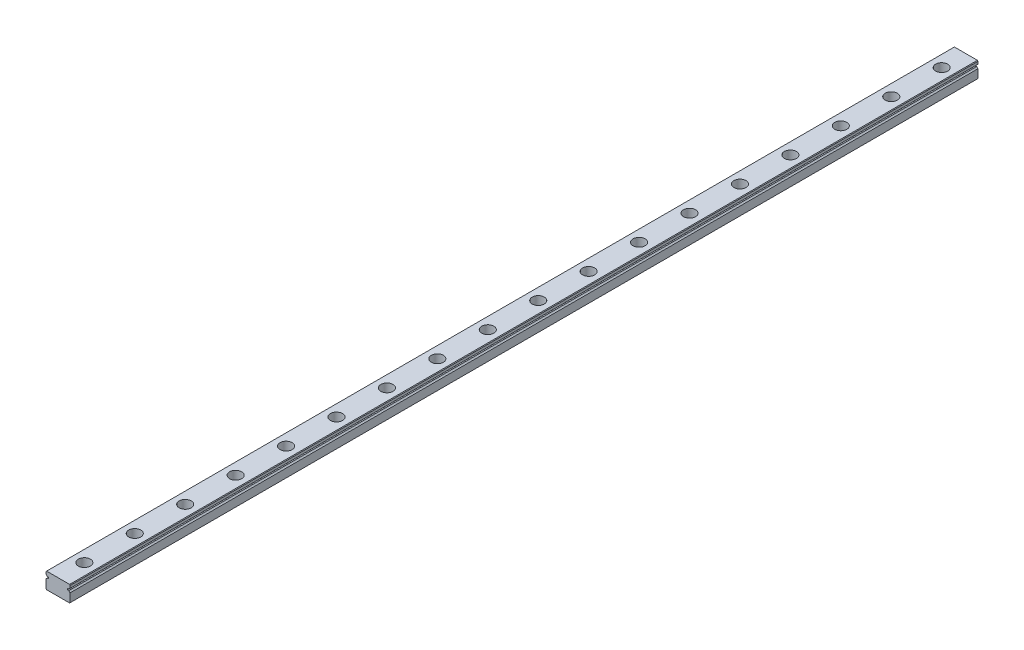
SolidWorks part; units mm, degrees
ref_plane "Спереди" through (0, 0, 0) normal (0, 0, 1) x (1, 0, 0)
ref_plane "Сверху" through (0, 0, 0) normal (0, 1, 0) x (1, 0, 0)
ref_plane "Справа" through (0, 0, 0) normal (1, 0, 0) x (0, 0, -1)
sketch "Эскиз1" plane through (0, 0, 0) normal (0, 0, 1) x (1, 0, 0)
  line L0 (-6, 3.7) -> (-5.7, 4)
  line L1 (-5.7, -4) -> (5.7, -4)
  line L2 (-6, -3.7) -> (-6, 0.549)
  line L3 (-5.7, 4) -> (5.7, 4)
  line L4 (6, -3.7) -> (6, 0.549)
  line L5 (-6, -4) -> (6, 4) construction
  line L6 (-6, 4) -> (6, -4) construction
  line L7 (-6, -3.7) -> (-5.7, -4)
  line L8 (5.7, -4) -> (6, -3.7)
  line L9 (5.7, 4) -> (6, 3.7)
  line L10 (-6, 2.451) -> (-6, 3.7)
  line L11 (-5.3546, 1.7981) -> (-4.6435, 1.7981)
  line L12 (0, 5.4188) -> (0, -5.747) construction
  line L13 (-5.3546, 1.2019) -> (-4.6435, 1.2019)
  line L14 (-4.6435, 1.7981) -> (-4.6435, 1.2019)
  line L15 (4.6435, 1.7981) -> (4.6435, 1.2019)
  line L16 (5.3546, 1.2019) -> (4.6435, 1.2019)
  line L17 (5.3546, 1.7981) -> (4.6435, 1.7981)
  line L18 (6, 2.451) -> (6, 3.7)
  line L19 (4.6435, 1.7981) -> (5.3546, 1.7981) construction
  arc A0 (-6, 0.549) -> (-5.3546, 1.2019) centre (-6.3091, 1.5) ccw
  arc A1 (-5.3546, 1.7981) -> (-6, 2.451) centre (-6.3091, 1.5) ccw
  arc A2 (5.3546, 1.7981) -> (6, 2.451) centre (6.3091, 1.5) cw
  arc A3 (6, 0.549) -> (5.3546, 1.2019) centre (6.3091, 1.5) cw
  point P0 (0, 0)
extrude "Бобышка-Вытянуть1" add sketch "Эскиз1" along normal blind 450
sketch "Эскиз2" plane through (0, 4, 0) normal (0, 1, 0) x (1, 0, 0)
  line L0 (0, 0) -> (0, -26.2396) construction
  line L1 (5.7, 0) -> (-5.7, 0) construction
  line L2 (-3.8306, -12) -> (3.8306, -12) construction
  circle A0 centre (0, -12) radius 3
  circle A1 centre (0, -12) radius 1.75
  dimension "D2" = 3.5
  dimension "D3" = 6
  dimension "D1" = 12
extrude "Вырез-Вытянуть1" cut sketch "Эскиз2" against normal blind 4.5
extrude "Вырез-Вытянуть2" cut sketch "Эскиз2<2>" against normal through all contours A1 region at (0, 4, 12)
sketch "Эскиз2<2>" plane through (0, 4, 0) normal (0, 1, 0) x (1, 0, 0) same geometry as "Эскиз2"
pattern_linear "Линейный массив1" count 24 spacing 25 along (0, 0, 1) of "Вырез-Вытянуть1", "Вырез-Вытянуть2"
